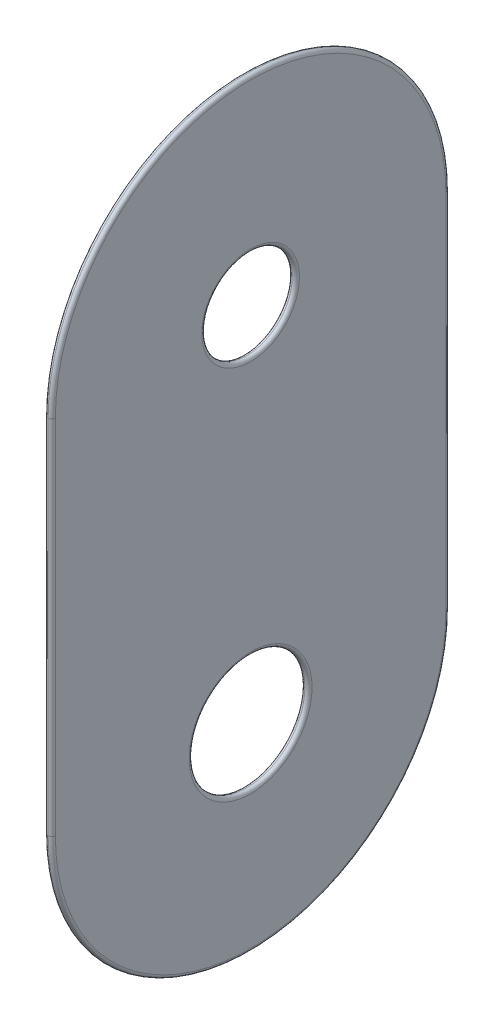
SolidWorks part; units mm, degrees
ref_plane "Front Plane" through (0, 0, 0) normal (0, 0, 1) x (1, 0, 0)
ref_plane "Top Plane" through (0, 0, 0) normal (0, 1, 0) x (1, 0, 0)
ref_plane "Right Plane" through (0, 0, 0) normal (1, 0, 0) x (0, 0, -1)
sketch "Sketch2" plane through (0, 0, 0) normal (1, 0, 0) x (0, 0, -1)
  line L0 (-31.7681, 0) -> (28.4393, 0) construction
  line L1 (0, 26.594) -> (0, -23.9889) construction
  line L2 (0, 12.7) -> (0, -12.7) construction
  line L3 (13.97, 12.7) -> (13.97, -12.7)
  line L4 (-13.97, 12.7) -> (-13.97, -12.7)
  circle A0 centre (0, 12.7) radius 3.175
  circle A1 centre (0, -12.7) radius 4.064
  arc A2 (13.97, 12.7) -> (-13.97, 12.7) centre (0, 12.7) ccw
  arc A3 (-13.97, -12.7) -> (13.97, -12.7) centre (0, -12.7) ccw
  point P9 (0, 0)
  dimension "D2" = 6.35
  dimension "D3" = 8.128
  dimension "D1" = 25.4
  dimension "D4" = 27.94
extrude "Boss-Extrude1" add sketch "Sketch2" along normal mid plane 0.508
fillet "Fillet1" radius 0.254 6 edges at (0.254, -12.7, -4.064) (0.254, 0, -13.97) (0.254, -26.67, 0) (0.254, 0, 13.97) (0.254, 26.67, 0) (0.254, 12.7, -3.175)
fillet "Fillet2" radius 0.254 6 edges at (-0.254, -12.7, -4.064) (-0.254, 12.7, -3.175) (-0.254, 0, 13.97) (-0.254, -26.67, 0) (-0.254, 0, -13.97) (-0.254, 26.67, 0)
